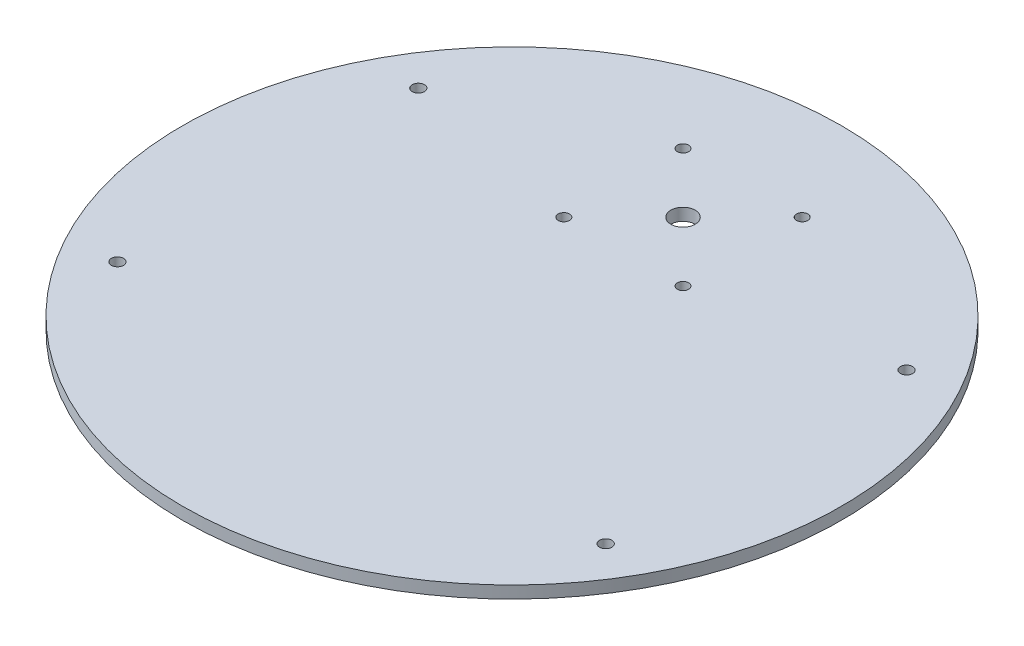
SolidWorks part; units mm, degrees
ref_plane "Front Plane" through (0, 0, 0) normal (0, 0, 1) x (1, 0, 0)
ref_plane "Top Plane" through (0, 0, 0) normal (0, 1, 0) x (1, 0, 0)
ref_plane "Right Plane" through (0, 0, 0) normal (1, 0, 0) x (0, 0, -1)
sketch "Sketch1" plane through (0, 0, 0) normal (0, 1, 0) x (1, 0, 0)
  circle A0 centre (0, 0) radius 85.725
  dimension "D1" = 171.45
extrude "Boss-Extrude1" add sketch "Sketch1" along normal blind 3.175
sketch "Sketch2" plane through (0, 3.175, 0) normal (0, 1, 0) x (1, 0, 0)
  line L0 (-63.5, 39.1325) -> (-63.5, -39.1325) construction
  line L1 (-63.5, -39.1325) -> (63.5, -39.1325) construction
  line L2 (63.5, -39.1325) -> (63.5, 39.1325) construction
  line L3 (63.5, 39.1325) -> (-63.5, 39.1325) construction
  circle A0 centre (-63.5, 39.1325) radius 1.5875
  circle A1 centre (63.5, 39.1325) radius 1.5875
  circle A2 centre (-63.5, -39.1325) radius 1.5875
  circle A3 centre (63.5, -39.1325) radius 1.5875
  dimension "D1" = 3.175
  dimension "D2" = 3.175
  dimension "D3" = 127
  dimension "D4" = 3.175
  dimension "D5" = 3.175
  dimension "D6" = 78.265
  dimension "D8" = 39.1325
  dimension "D9" = 63.5
extrude "Cut-Extrude1" cut sketch "Sketch2" against normal up to next
sketch "Sketch3" plane through (0, 3.175, 0) normal (0, 1, 0) x (1, 0, 0)
  line L0 (0, 44.4822) -> (0, 0) construction
  circle A0 centre (0, 44.4822) radius 3.175
  dimension "D1" = 6.35
  dimension "D2" = 44.4822
extrude "Cut-Extrude2" cut sketch "Sketch3" against normal up to next contours A0
ref_axis "Axis1" through (0, 3.175, 0) along (0, -1, 0)
sketch "Sketch5" plane through (0, 3.175, 0) normal (0, 1, 0) x (1, 0, 0)
  line L1 (-15.5004, 59.9825) -> (15.5003, 59.9825) construction
  line L2 (-15.5004, 59.9825) -> (-15.5003, 28.9818) construction
  line L3 (-15.5003, 28.9818) -> (15.5003, 28.9818) construction
  line L4 (15.5003, 59.9825) -> (15.5003, 28.9818) construction
  line L5 (-15.5004, 59.9825) -> (15.5003, 28.9818) construction
  line L6 (-15.5003, 28.9818) -> (15.5003, 59.9825) construction
  circle A0 centre (0, 44.4822) radius 3.175 construction
  circle A1 centre (0, 44.4822) radius 3.175 construction
  circle A2 centre (-15.5004, 59.9825) radius 1.4732
  circle A3 centre (15.5003, 59.9825) radius 1.4732
  circle A4 centre (-15.5003, 28.9818) radius 1.4732
  circle A5 centre (15.5003, 28.9818) radius 1.4732
  dimension "D3" = 2.9464
  dimension "D4" = 2.9464
  dimension "D5" = 2.9464
  dimension "D6" = 2.9464
  dimension "D1" = 31.0007
  dimension "D2" = 31.0007
extrude "Cut-Extrude3" cut sketch "Sketch5" against normal up to next
